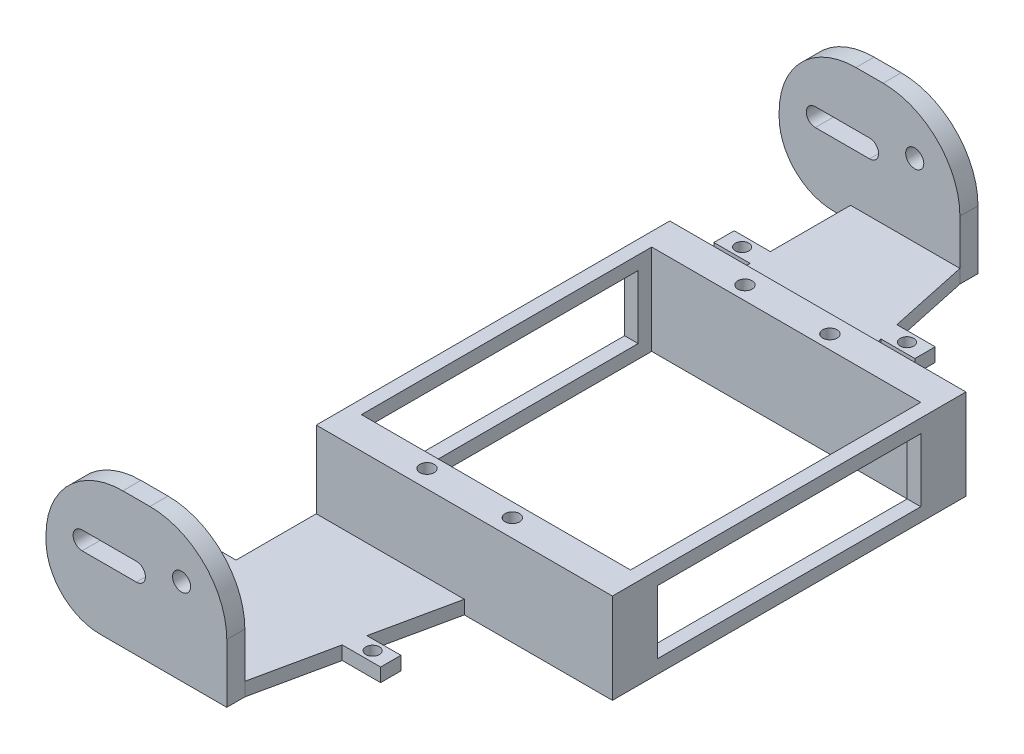
SolidWorks part; units mm, degrees
ref_plane "Front Plane" through (0, 0, 0) normal (0, 0, 1) x (1, 0, 0)
ref_plane "Top Plane" through (0, 0, 0) normal (0, 1, 0) x (1, 0, 0)
ref_plane "Right Plane" through (0, 0, 0) normal (1, 0, 0) x (0, 0, -1)
sketch "Sketch1" plane through (0, 0, 0) normal (0, 1, 0) x (1, 0, 0)
  line L0 (0, 39.1145) -> (0, -39.1145)
  line L1 (0, -39.1145) -> (65.532, -39.1145)
  line L2 (65.532, -39.1145) -> (65.532, 39.1145)
  line L3 (65.532, 39.1145) -> (0, 39.1145)
  line L4 (0, 39.1145) -> (0, 79.1145)
  line L5 (0, 79.1145) -> (24.2, 79.1145)
  line L6 (24.2, 79.1145) -> (32.766, 39.1145)
  line L7 (0, 39.1145) -> (32.766, 39.1145)
  line L8 (0, -39.1145) -> (0, -79.1145)
  line L9 (-8, 61.3645) -> (8, 61.3645)
  line L10 (-8, 61.3645) -> (-8, 56.8645)
  line L11 (-8, 56.8645) -> (8, 56.8645)
  line L12 (8, 61.3645) -> (8, 56.8645)
  line L13 (-55, 0) -> (55, 0) construction
  line L14 (3, 32.1145) -> (62.532, 32.1145)
  line L15 (20.483, 61.3645) -> (36.483, 61.3645)
  line L16 (20.483, 61.3645) -> (20.483, 56.8645)
  line L17 (20.483, 56.8645) -> (36.483, 56.8645)
  line L18 (36.483, 61.3645) -> (36.483, 56.8645)
  line L19 (3, 32.1145) -> (3, -32.1145)
  line L20 (3, -32.1145) -> (62.532, -32.1145)
  line L21 (0, -55) -> (0, 55) construction
  line L22 (0, -79.1145) -> (24.2, -79.1145)
  line L23 (24.2, -79.1145) -> (32.766, -39.1145)
  line L24 (32.766, -39.1145) -> (0, -39.1145)
  line L25 (62.532, 32.1145) -> (62.532, -32.1145)
  line L26 (20.483, -56.8645) -> (36.483, -56.8645)
  line L27 (20.483, -56.8645) -> (20.483, -61.3645)
  line L28 (20.483, -61.3645) -> (36.483, -61.3645)
  line L29 (36.483, -56.8645) -> (36.483, -61.3645)
  line L30 (3, 32.1145) -> (62.532, -32.1145) construction
  line L31 (3, -32.1145) -> (62.532, 32.1145) construction
  line L32 (-8, -56.8645) -> (8, -56.8645)
  line L33 (-8, -56.8645) -> (-8, -61.3645)
  line L34 (-8, -61.3645) -> (8, -61.3645)
  line L35 (8, -56.8645) -> (8, -61.3645)
  line L36 (0, 79.1145) -> (0, 81.1145)
  line L37 (0, 81.1145) -> (24.2, 81.1145)
  line L38 (24.2, 81.1145) -> (24.2, 79.1145)
  line L39 (0, -79.1145) -> (0, -81.0311)
  line L40 (0, -81.0311) -> (37.5753, -81.0311)
  line L41 (37.5753, -81.0311) -> (37.5753, -79.1145)
  line L42 (37.5753, -79.1145) -> (0, -79.1145)
  line L43 (32.766, 39.1145) -> (0, 39.1145)
  line L44 (32.766, -39.1145) -> (0, -39.1145)
  circle A0 centre (20.574, 35.1758) radius 1.6
  circle A1 centre (39.37, 35.1758) radius 1.5999
  circle A2 centre (20.574, -35.1795) radius 1.6
  circle A3 centre (39.4509, -35.1795) radius 1.5999
  circle A4 centre (-4, 59.1145) radius 1.5
  circle A5 centre (32.483, 59.1145) radius 1.5
  circle A6 centre (-4, -59.1145) radius 1.5
  circle A8 centre (32.483, -59.1145) radius 1.5
  point P8 (0, 59.1145)
  point P21 (28.483, 59.1145)
  point P30 (28.483, -59.1145)
  point P40 (0, -59.1145)
  point P47 (32.766, 0)
  dimension "D12" = 3
  dimension "D14" = 3
  dimension "D23" = 3
  dimension "D24" = 4
  dimension "D26" = 3
  dimension "D27" = 7
  dimension "D1" = 65.532
  dimension "D2" = 78.229
  dimension "D3" = 40
  dimension "D4" = 24.2
  dimension "D5" = 7
  dimension "D6" = 40
  dimension "D7" = 16
  dimension "D8" = 16
  dimension "D9" = 4.5
  dimension "D10" = 4.5
  dimension "D11" = 8
  dimension "D13" = 4
  dimension "D15" = 4
  dimension "D16" = 44.483
  dimension "D17" = 40
  dimension "D18" = 70.3553
  dimension "D19" = 16
  dimension "D20" = 16
  dimension "D21" = 4.5
  dimension "D22" = 4.5
  dimension "D25" = 4
  dimension "D28" = 3
  dimension "D29" = 3
  dimension "D30" = 2.25
  dimension "D31" = 2.25
  dimension "D32" = 2.25
  dimension "D33" = 2.25
  dimension "D34" = 36.483
  dimension "D35" = 36.483
  dimension "D36" = 2
  dimension "D37" = 3.935
extrude "Boss-Extrude1" add sketch "Sketch1" along normal blind 3 contours L10 L11 L4 L9 A4 | L12 L9 L4 L11 | L17 L16 L15 L6 L5 L4 L9 L12 L11 L3 | L16 L17 L6 L15 | L18 L15 L6 L17 A5 | L2 L3 L0 L1 A3 A2 A1 A0 L14 L25 L20 L19 | L32 L35 L34 L8 L22 L23 L28 L27 L26 L1 | L27 L28 L23 L26 | L29 L26 L23 L28 A8 | L35 L32 L8 L34 | L33 L34 L8 L32 A6 region at (16.383, 0, -38.094) region at (14.3559, 0, -58.0459) region at (14.3559, 0, 58.0459) region at (-4, 0, -56.9563) region at (4, 0, -59.1145) region at (4, 0, 59.1145) region at (-0.0918, 0, 59.1145) region at (24.4878, 0, -59.0693) region at (28.5769, 0, -59.1346) region at (32.7239, 0, 56.9605) region at (24.4878, 0, 59.0693)
sketch "Sketch2" plane through (0, 0, 0) normal (0, 1, 0) x (1, 0, 0)
  line L11 (24.2, -79.1145) -> (24.2, -83.1145)
  line L12 (24.2, -83.1145) -> (-15.8, -83.1145)
  line L13 (-15.8, -83.1145) -> (-15.8, -79.1145)
  line L14 (-15.8, -79.1145) -> (24.2, -79.1145)
  line L15 (24.2, 79.1145) -> (24.2, 83.1145)
  line L16 (24.2, 83.1145) -> (-15.8, 83.1145)
  line L17 (-15.8, 83.1145) -> (-15.8, 79.1145)
  line L18 (-15.8, 79.1145) -> (24.2, 79.1145)
  dimension "D1" = 40
  dimension "D2" = 4
  dimension "D3" = 40
  dimension "D4" = 4
extrude "Boss-Extrude2" add sketch "Sketch2" along normal blind 30
sketch "Sketch3" plane through (0, 0, 0) normal (0, 0, 1) x (1, 0, 0)
  line L0 (24.2, 30) -> (24.2, 0) construction
  line L1 (24.2, 3) -> (28.0012, 3) construction
  line L3 (-15.8, 30) -> (-15.8, 0) construction
  line L4 (-7.8, 18) -> (4.2, 18)
  line L8 (-7.8, 14) -> (4.2, 14)
  circle A0 centre (14.2, 19.1) radius 2
  circle A1 centre (-7.8, 16) radius 2
  circle A3 centre (4.2, 16) radius 2
  dimension "D1" = 4
  dimension "D4" = 4
  dimension "D6" = 13
  dimension "D2" = 10
  dimension "D3" = 16.1
  dimension "D5" = 8
  dimension "D7" = 12
extrude "Cut-Extrude1" cut sketch "Sketch3" against normal through all both and the other way through all contours A1 | A3 L4 A1 L8 | A3 | A0 region at (-1.8, 16, 0) region at (-7.8, 16, 0) region at (4.2, 16, 0) region at (14.2, 19.1, 0)
fillet "Fillet2" radius 17 4 edges at (-15.8, 30, -81.1145) (24.2, 30, -81.1145) (24.2, 30, 81.1145) (-15.8, 30, 81.1145)
fillet "Fillet3" radius 12 2 edges at (-15.8, 0, 81.1145) (-15.8, 0, -81.1145)
extrude "Boss-Extrude3" add sketch "Sketch1<8>" along normal blind 20 contours L2 L3 L0 L1 A3 A2 A1 A0 L14 L25 L20 L19 region at (16.383, 0, -38.094)
sketch "Sketch1<8>" plane through (0, 0, 0) normal (0, 1, 0) x (1, 0, 0) same geometry as "Sketch1"
sketch "Sketch5" plane through (0, 0, 0) normal (0, 1, 0) x (1, 0, 0)
  circle A0 centre (20.574, -35.1795) radius 2.5
  circle A1 centre (39.4509, -35.1795) radius 2.5
  circle A2 centre (20.574, 35.1758) radius 2.5
  circle A3 centre (39.37, 35.1758) radius 2.5
  dimension "D1" = 5
extrude "Cut-Extrude2" cut sketch "Sketch5" along normal blind 5
sketch "Sketch7" plane through (0, 0, 0) normal (1, 0, 0) x (0, 0, -1)
  line L0 (-29.1145, 17) -> (-29.1145, 3)
  line L1 (-29.1145, 3) -> (29.1145, 3)
  line L2 (29.1145, 3) -> (29.1145, 17)
  line L3 (29.1145, 17) -> (-29.1145, 17)
  line L4 (-39.1145, 20) -> (-39.1145, 0) construction
  line L5 (39.1145, 20) -> (39.1145, 0) construction
  line L6 (-39.1145, 20) -> (39.1145, 20) construction
  line L7 (55, 0) -> (-55, 0) construction
  dimension "D1" = 10
  dimension "D2" = 10
  dimension "D3" = 3
  dimension "D4" = 3
extrude "Cut-Extrude3" cut sketch "Sketch7" along normal through all
